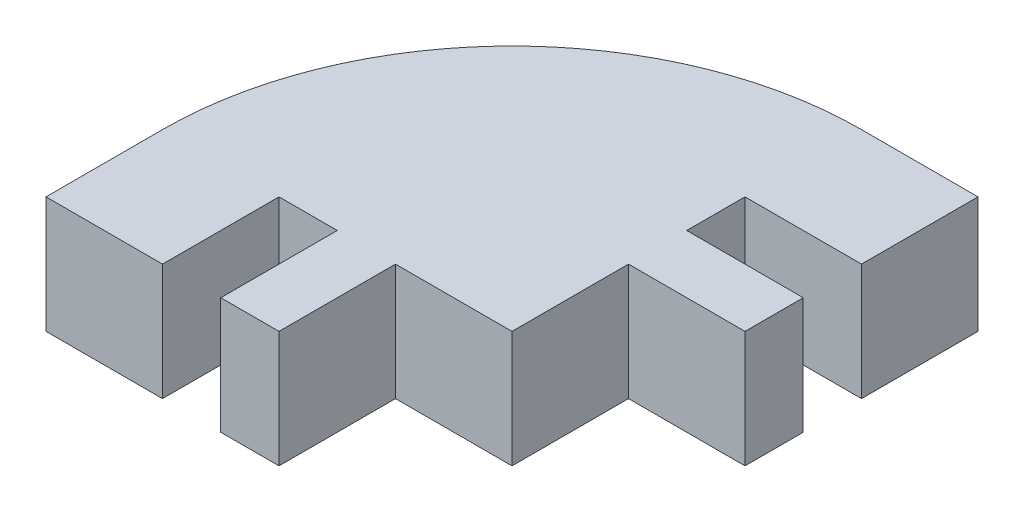
SolidWorks part; units mm, degrees
ref_plane "Front Plane" through (0, 0, 0) normal (0, 0, 1) x (1, 0, 0)
ref_plane "Top Plane" through (0, 0, 0) normal (0, 1, 0) x (1, 0, 0)
ref_plane "Right Plane" through (0, 0, 0) normal (1, 0, 0) x (0, 0, -1)
sketch "Sketch1" plane through (0, 0, 0) normal (0, 0, 1) x (1, 0, 0)
  line L0 (-125, 0) -> (125, 0) construction
  circle A0 centre (-125, 0) radius 4
  circle A1 centre (125, 0) radius 4
  circle A2 centre (-125, 0) radius 8
  circle A3 centre (125, 0) radius 8
  dimension "D1" = 8
  dimension "D3" = 16
  dimension "D2" = 250
extrude "Boss-Extrude1" add sketch "Sketch1" along normal blind 9
sketch "Sketch2" plane through (0, 0, 0) normal (0, 0, 1) x (1, 0, 0)
  line L0 (-125, -25) -> (125, -25) construction
  line L1 (0, -25) -> (0, -75) construction
  line L2 (-125, -75) -> (125, -75)
  line L3 (-125, -75) -> (-125, -25) construction
  line L4 (-175, 0) -> (-125, 0) construction
  line L5 (-175, 0) -> (-175, -75) construction
  line L6 (-125, 0) -> (125, 0) construction
  line L7 (-175, -75) -> (-125, -75)
  line L8 (-275, -75) -> (-175, -75) construction
  line L9 (225, -75) -> (125, -75) construction
  circle A0 centre (-125, 0) radius 25
  circle A1 centre (-125, 0) radius 4
  circle A2 centre (-125, 0) radius 4 construction
  circle A3 centre (125, 0) radius 4
  circle A4 centre (125, 0) radius 25
  circle A5 centre (125, 0) radius 4 construction
  circle A9 centre (-75, 0) radius 4
  circle A10 centre (-175, 0) radius 4
  circle A13 centre (-175, 0) radius 25
  circle A14 centre (-75, 0) radius 25
  circle A15 centre (-275, -75) radius 100
  circle A16 centre (225, -75) radius 100
  circle A17 centre (25, 187.5) radius 187.5
  circle A18 centre (-150, 43.3013) radius 25
  circle A19 centre (-100, 43.3013) radius 25
  dimension "D2" = 50
  dimension "D3" = 50
  dimension "D1" = 50
  dimension "D4" = 50
extrude "Boss-Extrude3" add sketch "Sketch2" along normal blind 9 contours A17 A14 A0 A13 A15 L7 L2 A16 A4 | A4 A3 | A14 A9 | A19 A0 A14 | A0 A1 | A18 A13 A0 | A13 A10 region at (-15.9174, -39.5028, 0) region at (106.5555, -15.8096, 0) region at (-193.176, 16.1176, 0) region at (-150, 14.4338, 0) region at (-146.0383, 12.1464, 0) region at (-54.169, 12.4986, 0) region at (-100, 14.4338, 0)
fillet "Fillet1" radius 1 2 edges at (125, -75, 4.5) (-175, -75, 4.5)
sketch "Sketch3" plane through (0, 0, 0) normal (0, 0, 1) x (1, 0, 0)
  line L0 (25, 0) -> (25, -75)
  line L1 (-174.005, -75) -> (124.005, -75) construction
  line L2 (25, -75) -> (150, -75)
  line L3 (150, -75) -> (150, 25)
  line L4 (150, 25) -> (25, 25)
  line L5 (25, 25) -> (25, 0)
  arc A0 (-63.2353, 22.0588) -> (113.2353, 22.0588) centre (25, 187.5) ccw construction
  arc A1 (145, -15) -> (113.2353, 22.0588) centre (125, 0) ccw construction
extrude "Cut-Extrude1" cut sketch "Sketch3" along normal through all
sketch "Sketch4" plane through (0, -75, 0) normal (0, -1, 0) x (1, 0, 0)
  line L0 (25, 9) -> (-63.2353, 9) construction
  line L1 (20.5, 9) -> (29.5, 9)
  line L2 (20.5, 9) -> (20.5, -18)
  line L3 (20.5, -18) -> (29.5, -18)
  line L4 (29.5, 9) -> (29.5, -18)
  line L5 (25, -18) -> (25, 9) construction
  dimension "D1" = 9
  dimension "D2" = 27
extrude "Boss-Extrude4" add sketch "Sketch4" against normal up to vertex (75 mm away) up to point (25, 0, 0)
sketch "Sketch5" plane through (0, 0, -18) normal (0, 0, -1) x (-1, 0, 0)
  line L0 (-125, -75) -> (-20.5, -75)
  line L1 (-20.5, -75) -> (-20.5, 0)
  line L2 (-20.5, 0) -> (-100, 0)
  circle A0 centre (-125, 0) radius 4
  circle A1 centre (-125, 0) radius 25
  circle A2 centre (-225, -75) radius 100
  circle A3 centre (-225, -75) radius 100 construction
  circle A4 centre (-125, 0) radius 25 construction
  circle A5 centre (-125, 0) radius 4 construction
  circle A6 centre (-25, 187.5) radius 187.5
  circle A7 centre (-25, 187.5) radius 187.5 construction
  line M4 (-29.5, -75) -> (-20.5, -75)
  line M5 (-20.5, -75) -> (-20.5, 0)
  line M6 (-20.5, 0) -> (-29.5, 0)
  line M7 (-29.5, 0) -> (-29.5, -75)
extrude "Boss-Extrude5" add sketch "Sketch5" along normal blind 9 contours A2 L0 L2 A1 M7 | A1 A0 | L2 M7 M4 M5 M6 | A6 A1 L2 region at (76.4581, -39.349, -18) region at (25, -37.5, -18) region at (143.4445, 15.8096, -18) region at (83.4345, 5.5048, -18)
sketch "Sketch6" plane through (0, 0, 0) normal (0, 0, -1) x (-1, 0, 0)
  line L0 (-20.5, 0) -> (-20.5, -25) construction
  line L1 (-20.5, 0) -> (-20.5, -75) construction
  line L2 (-20.5, -25) -> (-20.5, -50) construction
  line L3 (-20.5, -75) -> (-20.5, 0) construction
  line L4 (-20.5, -50) -> (-20.5, -75) construction
ref_plane "Plane1" through (0, -25, 0) normal (0, 1, 0) x (1, 0, 0)
ref_plane "Plane2" through (0, -50, 0) normal (0, 1, 0) x (1, 0, 0)
sketch "Sketch7" plane through (0, -25, 0) normal (0, 1, 0) x (1, 0, 0)
  line L0 (56.5, 18) -> (29.5, 18)
  line L1 (29.5, 18) -> (29.5, -9)
  line L2 (20.5, 27) -> (20.5, 0)
  line L3 (20.5, 0) -> (-6.5, 0)
  circle A0 centre (20.5, 0) radius 27
  circle A1 centre (29.5, 18) radius 27
extrude "Boss-Extrude6" add sketch "Sketch7" along normal blind 4.5 and the other way blind 4.5 contours L1 A1 A0 L0 | A0 A1 L0 | A1 A0 L3 | A0 A1 L3 L2 region at (49.8154, -25, -11.0447) region at (37.3919, -25, -4.7267) region at (0.1846, -25, -6.9553) region at (12.6081, -25, -13.2733)
extrude "Boss-Extrude7" add sketch "Sketch7<3>" along normal blind 4.5 and the other way blind 4.5 from surface contours A0 A1 L0 | L1 A1 A0 L0 | A0 A1 L3 L2 | A1 A0 L3 region at (49.8154, -25, -11.0447) region at (37.3919, -25, -4.7267) region at (0.1846, -25, -6.9553) region at (12.6081, -25, -13.2733) starting at plane "Plane2"
sketch "Sketch7<3>" plane through (0, -25, 0) normal (0, 1, 0) x (1, 0, 0) same geometry as "Sketch7"
sketch "Sketch9" plane through (0, 0, 9) normal (0, 0, 1) x (1, 0, 0)
  line L0 (-174.005, -75) -> (29.5, -75) construction
  line L1 (-164.7085, -50) -> (-155.7085, -50)
  line L2 (-164.7085, -50) -> (-164.7085, -57)
  line L3 (-164.7085, -57) -> (-155.7085, -57)
  line L4 (-155.7085, -50) -> (-155.7085, -57)
  line L5 (-164.7085, -66) -> (-155.7085, -66)
  line L6 (-164.7085, -66) -> (-164.7085, -75)
  line L7 (-164.7085, -75) -> (-155.7085, -75)
  line L8 (-155.7085, -66) -> (-155.7085, -75)
  line L9 (-155.7085, -75) -> (-155.7085, -66) construction
  line L10 (-20.8518, -75) -> (-20.8518, -66) construction
  line L11 (-29.8518, -50) -> (-20.8518, -50)
  line L12 (-29.8518, -50) -> (-29.8518, -57)
  line L13 (-29.8518, -57) -> (-20.8518, -57)
  line L14 (-20.8518, -50) -> (-20.8518, -57)
  line L15 (-29.8518, -66) -> (-20.8518, -66)
  line L16 (-29.8518, -66) -> (-29.8518, -75)
  line L17 (-29.8518, -75) -> (-20.8518, -75)
  line L18 (-20.8518, -66) -> (-20.8518, -75)
  line L19 (125, -75) -> (29.5, -75) construction
  line L20 (105.005, -50) -> (114.005, -50)
  line L21 (105.005, -50) -> (105.005, -57)
  line L22 (105.005, -57) -> (114.005, -57)
  line L23 (114.005, -50) -> (114.005, -57)
  line L24 (105.005, -66) -> (114.005, -66)
  line L25 (105.005, -66) -> (105.005, -75)
  line L26 (105.005, -75) -> (114.005, -75)
  line L27 (114.005, -66) -> (114.005, -75)
extrude "Cut-Extrude2" cut sketch "Sketch9" against normal through all
sketch "Sketch10" plane through (0, -20.5, 0) normal (0, 1, 0) x (1, 0, 0)
  line L0 (20.5, 27) -> (29.5, 27)
  line L1 (113.2353, 27) -> (25, 27) construction
  line L2 (29.5, 27) -> (29.5, 18)
  line L3 (56.5, 18) -> (29.5, 18) construction
  line L4 (29.5, 18) -> (20.5, 18)
  line L5 (20.5, 27) -> (20.5, 0) construction
  line L6 (20.5, 18) -> (20.5, 13.5)
  line L7 (20.5, 0) -> (20.5, 27) construction
  line L8 (20.5, 13.5) -> (29.5, 13.5)
  line L9 (29.5, 18) -> (29.5, -9) construction
  line L10 (29.5, 13.5) -> (29.5, 4.5)
  line L11 (29.5, 18) -> (29.5, -9) construction
  line L12 (29.5, 4.5) -> (20.5, 4.5)
  line L13 (20.5, 4.5) -> (20.5, 0)
  line L14 (20.5, 0) -> (11.5, 0)
  line L15 (25, 0) -> (-63.2353, 0) construction
  line L16 (11.5, 0) -> (11.5, -9)
  line L17 (-63.2353, -9) -> (25, -9) construction
  line L18 (11.5, -9) -> (7, -9)
  line L19 (7, -9) -> (7, 0)
  line L20 (7, 0) -> (2.5, 0)
  line L21 (2.5, 0) -> (2.5, -9)
  line L22 (2.5, -9) -> (-6.5, -9)
  line L23 (-6.5, -9) -> (-6.5, 0)
  line L24 (29.5, 18) -> (29.5, 13.5) construction
  line L25 (7, -9) -> (2.5, -9) construction
  line L26 (20.5, 0) -> (20.5, -9)
  line L27 (20.5, -9) -> (29.5, -9)
  line L28 (29.5, -9) -> (29.5, 0)
  line L29 (29.5, 0) -> (20.5, 0)
  line L30 (29.5, 18) -> (29.5, 0)
  line L31 (20.5, 27) -> (20.5, 0)
  line L32 (2.5, 0) -> (20.5, 0)
  line L33 (2.5, -9) -> (20.5, -9)
  line L34 (29.5, 9) -> (20.5, 9)
  line L35 (25, 18) -> (25, 13.5) construction
  line L36 (25, 13.5) -> (25, 9) construction
  line L37 (25, 9) -> (25, 4.5) construction
  line L38 (25, 0) -> (25, 4.5) construction
  line L40 (166.2069, 69.3754) -> (-211.856, 69.3754)
  line L41 (166.2069, 69.3754) -> (166.2069, -51.9781)
  line L42 (166.2069, -51.9781) -> (-211.856, -51.9781)
  line L43 (-211.856, 69.3754) -> (-211.856, -51.9781)
  circle A0 centre (20.5, 0) radius 27
  arc A1 (20.5, 27) -> (-6.5, 0) centre (20.5, 0) ccw construction
  circle A2 centre (29.5, 18) radius 27
  arc A3 (29.5, -9) -> (56.5, 18) centre (29.5, 18) ccw construction
  line M9 (-6.5, 0) -> (20.5, 0)
  line M10 (20.5, 0) -> (20.5, 27)
  arc M11 (20.5, 27) -> (-6.5, 0) centre (20.5, 0) ccw
  dimension "D1" = 9
  dimension "D2" = 4.5
  dimension "D3" = 4.5
extrude "Cut-Extrude3" cut sketch "Sketch10" along normal through all both and the other way through all contours L40 L43 L42 L41 A2 A0 L22 L23 | L28 A2 A0 L2 L30 L10 | A0 A2 L0 L2 M11 | L21 L33 L19 M9 | L30 L4 L8 M10 | L30 L34 L12 M10 | L30 L12 L29 M10 | L16 A2 L26 M9 | A2 L16 L33 L26 | A2 L26 L27 | L26 A2 L28 L29 region at (34.7456, -20.5, -28.4347) region at (25, -20.5, -15.75) region at (36.977, -20.5, -6.4418) region at (25, -20.5, -6.75) region at (4.75, -20.5, 4.5) region at (16.7628, -20.5, 2.8202) region at (14.9622, -20.5, 6.7854) region at (25, -20.5, -2.25) region at (25.1356, -20.5, 4.258) region at (22.7369, -20.5, 8.5391) region at (-26.5954, -20.5, -8.6765)
sketch "Sketch11" plane through (0, 0, 0) normal (0, 0, 1) x (1, 0, 0)
  line L0 (20.5, -20.5) -> (-6.5, -20.5) construction
  line L1 (32.1397, 6.8082) -> (-8.9043, 6.8082)
  line L2 (32.1397, 6.8082) -> (32.1397, -77.2228)
  line L3 (32.1397, -77.2228) -> (-8.9043, -77.2228)
  line L4 (-8.9043, 6.8082) -> (-8.9043, -77.2228)
  line L5 (-8.9043, -20.5) -> (32.1397, -20.5)
  line L6 (-8.9043, -20.5) -> (-8.9043, -29.5)
  line L7 (-8.9043, -29.5) -> (32.1397, -29.5)
  line L8 (32.1397, -20.5) -> (32.1397, -29.5)
  line L9 (-6.5, -29.5) -> (20.5, -29.5) construction
  point P9 (-8.9043, -20.6009)
extrude "Cut-Extrude4" cut sketch "Sketch11" against normal through all both and the other way through all contours L4 L5 L2 L1 | L7 L4 L3 L2 region at (11.6177, -6.8459, 0) region at (11.6177, -53.3614, 0)
